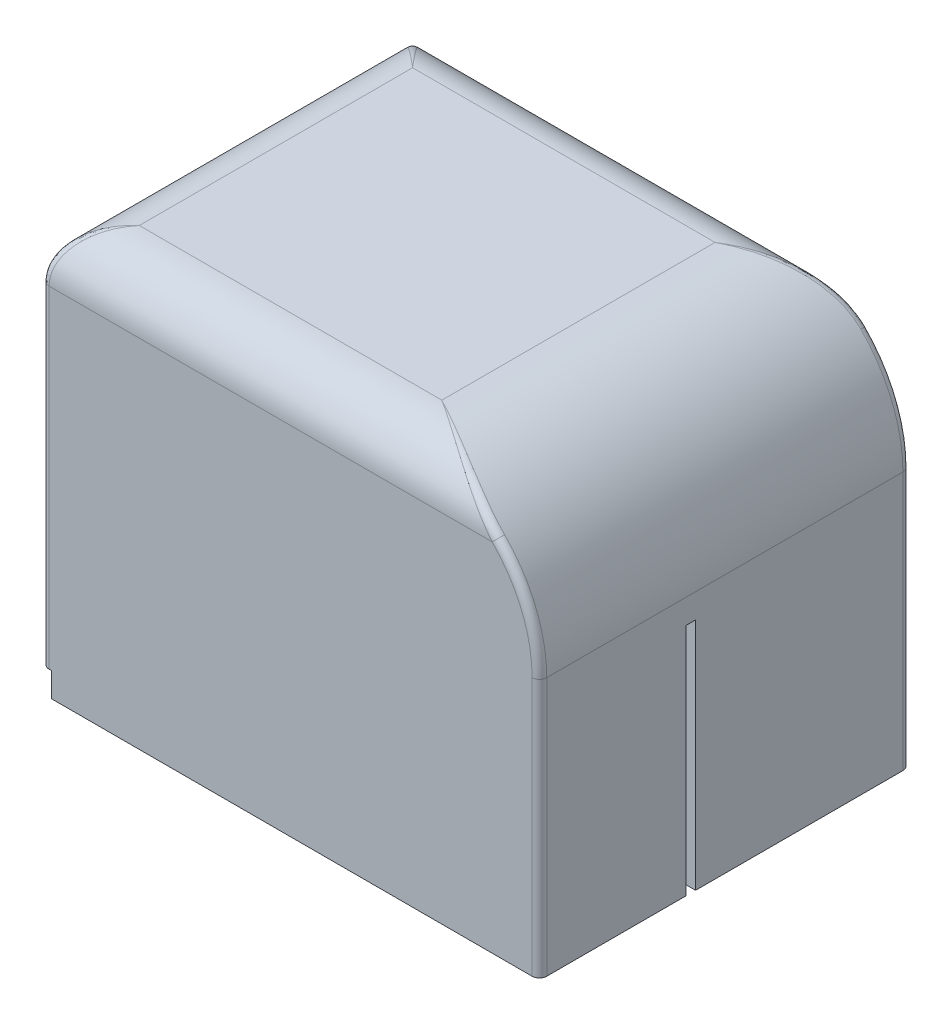
SolidWorks part; units mm, degrees
ref_plane "Front" through (0, 0, 0) normal (0, 0, 1) x (1, 0, 0)
ref_plane "Top" through (0, 0, 0) normal (0, 1, 0) x (1, 0, 0)
ref_plane "Right" through (0, 0, 0) normal (1, 0, 0) x (0, 0, -1)
sketch "Sketch1" plane through (0, 0, 0) normal (0, 1, 0) x (1, 0, 0)
  line L0 (-51, 38) -> (51, 38)
  line L1 (-49, 36) -> (49, 36)
  line L2 (-49, 36) -> (-49, -36)
  line L3 (-49, -36) -> (49, -36)
  line L4 (49, 36) -> (49, -36)
  line L5 (-49, 36) -> (49, -36) construction
  line L6 (-49, -36) -> (49, 36) construction
  line L7 (51, 38) -> (51, -38)
  line L8 (-51, -38) -> (51, -38)
  line L9 (-51, 38) -> (-51, -38)
  point P0 (0, 0)
  dimension "D1" = 98
  dimension "D2" = 72
  dimension "D3" = 2
extrude "Boss-Extrude1" add sketch "Sketch1" along normal blind 80
sketch "Sketch2" plane through (51, 0, 0) normal (1, 0, 0) x (0, 0, -1)
  line L0 (-8, 0) -> (-8, 48)
  line L1 (-38, 0) -> (38, 0) construction
  line L2 (-8, 48) -> (-6, 48)
  line L3 (-6, 48) -> (-6, 0)
  line L4 (-38, 80) -> (-38, 0) construction
  line L5 (-8, 0) -> (-6, 0)
  dimension "D1" = 2
  dimension "D2" = 30
  dimension "D3" = 48
extrude "Cut-Extrude1" cut sketch "Sketch2" against normal blind 5 and the other way through all
sketch "Sketch3" plane through (0, 0, -38) normal (0, 0, -1) x (-1, 0, 0)
  line L0 (-15, 0) -> (-15, 23)
  line L1 (-51, 0) -> (51, 0) construction
  line L2 (-15, 23) -> (41, 23)
  line L3 (41, 23) -> (41, 0)
  line L4 (51, 80) -> (51, 0) construction
  line L5 (-15, 0) -> (41, 0)
  dimension "D1" = 23
  dimension "D2" = 56
  dimension "D3" = 10
extrude "Cut-Extrude3" cut sketch "Sketch3" against normal blind 5
sketch "Sketch4" plane through (-51, 0, 0) normal (-1, 0, 0) x (0, 0, 1)
  line L0 (-38, 5) -> (-15, 5)
  line L1 (-38, 80) -> (-38, 0) construction
  line L2 (-15, 5) -> (-15, 42)
  line L3 (-15, 42) -> (17, 42)
  line L4 (17, 42) -> (17, 5)
  line L5 (17, 5) -> (38, 5)
  line L6 (38, 80) -> (38, 0) construction
  line L7 (38, 5) -> (38, 0)
  line L8 (38, 0) -> (-38, 0)
  line L9 (-38, 0) -> (-38, 5)
  dimension "D1" = 23
  dimension "D2" = 32
  dimension "D3" = 42
  dimension "D4" = 5
extrude "Cut-Extrude4" cut sketch "Sketch4" against normal blind 2
sketch "Sketch5" plane through (0, 80, 0) normal (0, 1, 0) x (1, 0, 0)
  line L0 (-51, -38) -> (51, -38) construction
  line L1 (51, -38) -> (51, 38) construction
  line L2 (-51, 38) -> (-51, -38) construction
  line L3 (51, 38) -> (-51, 38) construction
  line L4 (-51, -38) -> (51, -38)
  line L5 (51, -38) -> (51, 38)
  line L6 (-51, 38) -> (-51, -38)
  line L7 (51, 38) -> (-51, 38)
extrude "Boss-Extrude2" add sketch "Sketch5" along normal blind 3
fillet "Fillet3" radius 10 6 edges at (0, 80, -36) (0, 80, 36) (-49, 80, 0) (0, 83, -38) (-51, 83, 0) (0, 83, 38)
fillet "Fillet5" radius 30 2 edges at (51, 83, 0) (49, 80, 0)
fillet "Fillet6" radius 1.5 10 edges at (-48.0711, 80.0711, -35.0711) (-48.0711, 80.0711, 35.0711) (32.9578, 80.5138, 34.5987) (49.0252, 63.7047, 38) (32.9578, 80.5138, -34.5987) (49.0252, 63.7047, -38) (-51, 39, -38) (-51, 39, 38) (51, 26.5, 38) (51, 26.5, -38)
